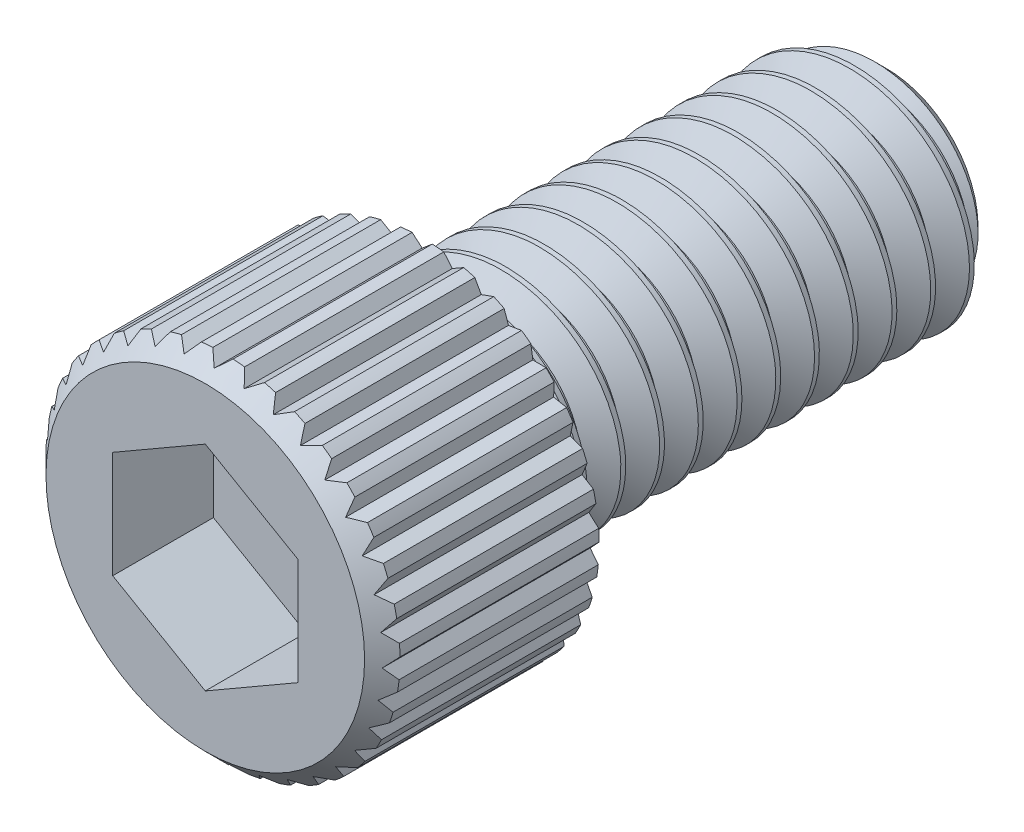
SolidWorks part; units mm, degrees
ref_plane "Front Plane" through (0, 0, 0) normal (0, 0, 1) x (1, 0, 0)
ref_plane "Top Plane" through (0, 0, 0) normal (0, 1, 0) x (1, 0, 0)
ref_plane "Right Plane" through (0, 0, 0) normal (1, 0, 0) x (0, 0, -1)
sketch "Sketch1" plane through (0, 0, 0) normal (1, 0, 0) x (0, 0, -1)
  line L0 (-4.4, 0) -> (4.4, 0) construction
  line L1 (-4.4, -2.285) -> (-4.4, 2.285) construction
  line L2 (-4.4, 2.285) -> (-1.6, 2.285) construction
  line L3 (4.4, -1.5) -> (4.4, 1.5) construction
  line L4 (4.3687, 1.5541) -> (4.8687, 1.5541) construction
  line L5 (4.8687, 1.5541) -> (4.6187, 1.1211) construction
  line L6 (4.6187, 1.1211) -> (4.3687, 1.5541) construction
  line L7 (4.6187, 1.5541) -> (4.6187, 1.5) construction
  line L8 (4.6187, 1.5) -> (4.6187, 1.1752) construction
  line L9 (4.6187, 1.1752) -> (4.6187, 1.1211) construction
  line L10 (4.3844, 1.5271) -> (4.8531, 1.5271) construction
  line L11 (4.5875, 1.1752) -> (4.65, 1.1752) construction
  line L12 (4.4, 1.5) -> (4.8375, 1.5) construction
  line L13 (-1.6, 2.285) -> (-1.6, 0) construction
  point P4 (0, 0)
  point P8 (-4.4, 0)
  point P9 (-4.4, 1.195)
  point P11 (-4.4, -1.195)
  point P14 (3.15, -1.5)
  point P16 (4.4, 0)
  point P19 (-3.1, 0)
  point P22 (4.6187, 1.5271)
  point P25 (4.6187, 1.1752)
  point P28 (4.6187, 1.5)
  dimension "Head Diameter" = 4.57
  dimension "Length" = 6
  dimension "Head Height" = 2.8
  dimension "Drive Size" = 2.39
  dimension "Thread Size" = 3
  dimension "Thread Pitch" = 0.5
  dimension "D1" = 0.0625
  dimension "D2" = 1.25
  dimension "HEX DEPTH" = 1.3
sketch "Sketch2" plane through (0, 0, 0) normal (1, 0, 0) x (0, 0, -1)
  line L0 (-4.4, 1.195) -> (-3.1, 1.195)
  line L1 (-3.1, 1.195) -> (-3.1, 0)
  line L2 (-4.4, 0) -> (4.4, 0) construction
  line L3 (-3.1, 0) -> (4.4, 0)
  line L4 (4.4, 0) -> (4.4, 1.1752)
  line L5 (4.4, -1.5) -> (4.4, 1.5) construction
  line L6 (4.4, 1.1752) -> (4.0752, 1.5)
  line L7 (4.0752, 1.5) -> (-1.6, 1.5)
  line L9 (-1.6, 1.5) -> (-1.6, 2.285)
  line L10 (-1.6, 2.285) -> (-4.1715, 2.285)
  line L11 (-4.4, 2.0565) -> (-4.4, 1.195)
  line L12 (-4.4, 0) -> (4.4, 0) construction
  line L13 (-4.4, 2.0565) -> (-4.1715, 2.285)
  dimension "D1" = 45
  dimension "D3" = 0.2285
  dimension "D4" = 45
revolve "Revolve1" add sketch "Sketch2" angle 360 about L12
sketch "Sketch3" plane through (0, 0, 4.4) normal (0, 0, 1) x (1, 0, 0)
  line L1 (0, 1.3799) -> (-1.195, 0.6899)
  line L2 (-1.195, 0.6899) -> (-1.195, -0.6899)
  line L3 (-1.195, -0.6899) -> (0, -1.3799)
  line L4 (0, -1.3799) -> (1.195, -0.6899)
  line L5 (1.195, -0.6899) -> (1.195, 0.6899)
  line L6 (1.195, 0.6899) -> (0, 1.3799)
  circle A0 centre (0, 0) radius 1.195 construction
  circle A1 centre (0, 0) radius 2.285 construction
  circle A2 centre (0, 0) radius 2.285 construction
extrude "Cut-Extrude1" cut sketch "Sketch3" against normal up to vertex (1.3 mm away) up to point (0, 0, 3.1)
sketch "Sketch6" plane through (0, 0, -4.4) normal (0, 0, -1) x (-1, 0, 0)
  circle A0 centre (0, 0) radius 1.5
split "Split1" bodies to split 105 resulting bodies 112 113 split by face at (2.285, 0, 1.6)
curve "Helix/Spiral1" pitch 0.5 height 6.5 radius 1.5 centre (0, 0, -4.4) axis (0, 0, 1) start towards (0, 1, 0)
sketch "Sketch7" plane through (0, 0, 0) normal (1, 0, 0) x (0, 0, -1)
  line L0 (4.3844, 1.5271) -> (4.8531, 1.5271)
  line L1 (4.8531, 1.5271) -> (4.65, 1.1752)
  line L2 (4.65, 1.1752) -> (4.5875, 1.1752)
  line L3 (4.5875, 1.1752) -> (4.3844, 1.5271)
sweep "Cut-Sweep1" cut profiles "Sketch7" path "Helix/Spiral1" align with end faces yes
sketch "Sketch10" plane through (0, 0, 1.6) normal (0, 0, -1) x (-1, 0, 0)
  circle A0 centre (0, 0) radius 1.5541
extrude "Boss-Extrude1" add sketch "Sketch10" along normal through all draft 45
sketch "Sketch9" plane through (0, 0, 4.4) normal (0, 0, 1) x (1, 0, 0)
  line L0 (0, 0) -> (0, 2.0565) construction
  line L1 (0, 2.0565) -> (0, 2.285) construction
  line L2 (0, 2.285) -> (0, 2.3993) construction
  line L3 (0, 2.3993) -> (0.2696, 2.3992)
  line L4 (0, 2.3993) -> (-0.2696, 2.3993)
  line L5 (0.2696, 2.3992) -> (0, 2.1707)
  line L6 (-0.2696, 2.3993) -> (0, 2.1707)
  line L7 (-0.1348, 2.285) -> (0, 2.285) construction
  line L8 (0, 2.285) -> (0.1348, 2.285) construction
  circle A0 centre (0, 0) radius 2.0565 construction
  circle A1 centre (0, 0) radius 2.285 construction
  dimension "D1" = 0.2696
extrude "Cut-Extrude4" cut sketch "Sketch9" against normal through all both and the other way through all
pattern_circular "CirPattern1" count 35 over 360 about axis through (0, 0, 4.4) along (0, 0, 1) of "Cut-Extrude4"
equation "\"D1@Sketch1\"=\"Thread Pitch@Sketch1\"/8"
equation "\"D3@Sketch2\"=\"Head Diameter@Sketch1\"*0.05"
equation "\"D3@Helix/Spiral1\"=\"Length@Sketch1\"+\"Thread Pitch@Sketch1\""
equation "\"D4@Helix/Spiral1\"=\"Thread Pitch@Sketch1\""
equation "\"D2@Sketch1\"=\"Thread Pitch@Sketch1\"*2.5"
equation "\"D1@Sketch9\"=\"Head Diameter@Sketch1\"*.059"
equation "\"D1@CirPattern1\"=((\"Head Diameter@Sketch1\"/1.5)/\"D1@Sketch9\")*pi"
